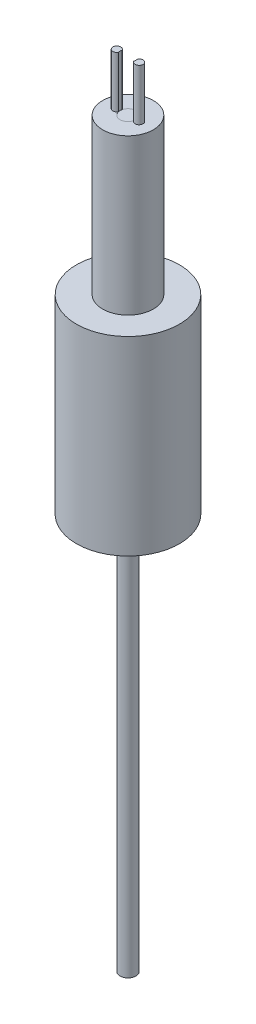
SolidWorks part; units mm, degrees
ref_plane "前视基准面" through (0, 0, 0) normal (0, 0, 1) x (1, 0, 0)
ref_plane "上视基准面" through (0, 0, 0) normal (0, 1, 0) x (1, 0, 0)
ref_plane "右视基准面" through (0, 0, 0) normal (1, 0, 0) x (0, 0, -1)
other "Configuration Table"
sketch "Sketch1" plane through (0, 0, 0) normal (0, 1, 0) x (1, 0, 0)
  circle A0 centre (0, 0) radius 3.2
  circle A1 centre (0, 0) radius 6.5
  circle A2 centre (1.4059, 0) radius 0.5
  circle A4 centre (-1.4059, 0) radius 0.5
  circle A5 centre (0, 0) radius 1
extrude "Boss-Extrude1" add sketch "Sketch1" along normal blind 50.1 contours A2 | A4 region at (1.4244, 0, 0) region at (-1.4244, 0, 0)
extrude "Boss-Extrude2" add sketch "Sketch1<3>" along normal blind 43.6 contours A0 A4 A2 region at (-3.1095, 0, 0)
sketch "Sketch1<3>" plane through (0, 0, 0) normal (0, 1, 0) x (1, 0, 0) same geometry as "Sketch1"
extrude "Boss-Extrude3" add sketch "Sketch1<4>" along normal blind 24 contours A1 A0 region at (-6.3162, 0, 0)
sketch "Sketch1<4>" plane through (0, 0, 0) normal (0, 1, 0) x (1, 0, 0) same geometry as "Sketch1"
extrude "Boss-Extrude4" add sketch "Sketch1<5>" against normal blind 50 and the other way blind 43.6 separate body contours A2 A5 A4 | A4 A5 | A2 A5 region at (0.9561, 0, 0) region at (0, 0, 0) region at (-0.9561, 0, 0)
sketch "Sketch1<5>" plane through (0, 0, 0) normal (0, 1, 0) x (1, 0, 0) same geometry as "Sketch1"
